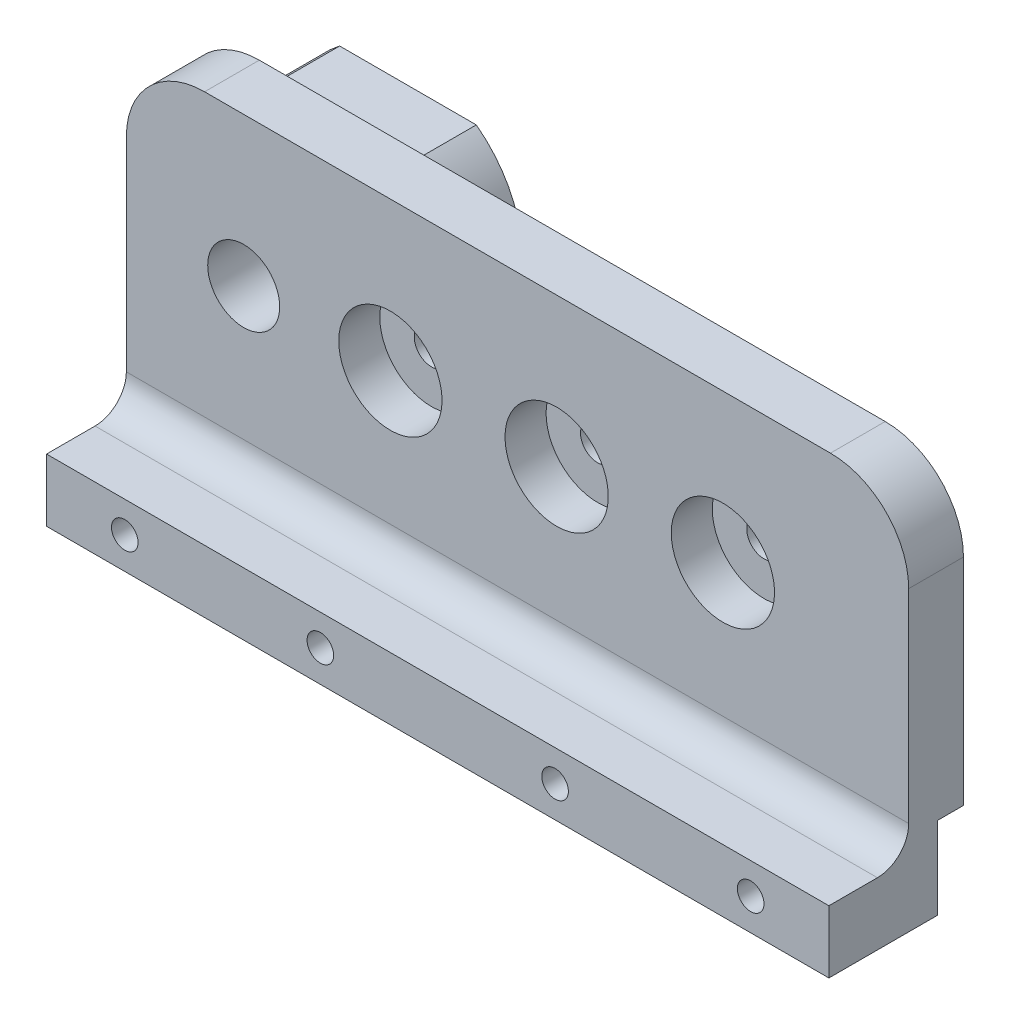
SolidWorks part; units mm, degrees
ref_plane "Front Plane" through (0, 0, 0) normal (0, 0, 1) x (1, 0, 0)
ref_plane "Top Plane" through (0, 0, 0) normal (0, 1, 0) x (1, 0, 0)
ref_plane "Right Plane" through (0, 0, 0) normal (1, 0, 0) x (0, 0, -1)
sketch "Sketch1" plane through (0, 0, 0) normal (0, 0, 1) x (1, 0, 0)
  line L1 (0, 0) -> (100, 0)
  line L2 (0, 0) -> (0, 48)
  line L3 (0, 48) -> (100, 48)
  line L4 (100, 0) -> (100, 48)
  dimension "D1" = 100
  dimension "D2" = 48
extrude "Boss-Extrude1" add sketch "Sketch1" along normal blind 7
sketch "Sketch2" plane through (0, 0, 7) normal (0, 0, 1) x (1, 0, 0)
  line L0 (0, 0) -> (100, 0) construction
  line L1 (0, 48) -> (0, 0) construction
  circle A0 centre (15, 29) radius 4.6
  circle A1 centre (33.75, 29) radius 2.2
  circle A2 centre (55, 29) radius 2.2
  circle A3 centre (76.25, 29) radius 2.2
  dimension "D1" = 4.4
  dimension "D2" = 18.75
  dimension "D3" = 21.25
  dimension "D4" = 21.25
  dimension "D5" = 29
  dimension "D6" = 15
  dimension "D7" = 9.2
extrude "Cut-Extrude1" cut sketch "Sketch2" against normal up to next
sketch "Sketch3" plane through (0, 0, 0) normal (0, 0, -1) x (-1, 0, 0)
  line L0 (0, 48) -> (0, 0) construction
  line L1 (-100, 0) -> (0, 0)
  line L2 (-100, 0) -> (-100, 8)
  line L3 (-100, 8) -> (0, 8)
  line L4 (0, 0) -> (0, 8)
  dimension "D1" = 8
extrude "Boss-Extrude2" add sketch "Sketch3" along normal blind 10.2
sketch "Sketch4" plane through (0, 0, 0) normal (0, 0, -1) x (-1, 0, 0)
  circle A0 centre (-76.25, 29) radius 6.6
  circle A1 centre (-55, 29) radius 6.6
  circle A2 centre (-33.75, 29) radius 6.6
  dimension "D1" = 13.2
extrude "Cut-Extrude2" cut sketch "Sketch4" against normal blind 5.25
sketch "Sketch5" plane through (0, 0, 7) normal (0, 0, 1) x (1, 0, 0)
  line L0 (35, 4.0521) -> (65, 4) construction
  line L1 (0, 0) -> (100, 0) construction
  circle A0 centre (35, 4.0521) radius 2.6
  circle A1 centre (65, 4) radius 2.6
  point P6 (50, 0)
  point P7 (50, 4.0261)
  dimension "D1" = 5.2
  dimension "D2" = 30
  dimension "D3" = 4
extrude "Cut-Extrude3" cut sketch "Sketch5" against normal blind 0.1
sketch "Sketch7" plane through (0, 0, 6.9) normal (0, 0, 1) x (1, 0, 0)
  circle A0 centre (35, 4.0521) radius 1.7
  circle A1 centre (65, 4) radius 1.7
  dimension "D1" = 3.4
extrude "Cut-Extrude4" cut sketch "Sketch7" against normal through all
sketch "Sketch8" plane through (0, 0, 7) normal (0, 0, 1) x (1, 0, 0)
  line L0 (10, 4.0521) -> (35, 4.0521) construction
  line L1 (0, 48) -> (0, 0) construction
  line L2 (100, 0) -> (100, 48) construction
  circle A0 centre (10, 4.0521) radius 1.7
  circle A1 centre (90, 4.0521) radius 1.7
  dimension "D1" = 3.4
  dimension "D2" = 10
  dimension "D3" = 10
extrude "Cut-Extrude5" cut sketch "Sketch8" against normal up to next
mirror "Mirror1" about plane through (0, 0, -10.2) normal (0, 0, 1) of bodies 110
delete or keep bodies "Body-Delete/Keep 1" type delete bodies bodies 110
sketch "Sketch9" plane through (100, 0, 0) normal (1, 0, 0) x (0, 0, -1)
  line L1 (27.4, 0) -> (24.1, 0)
  line L2 (27.4, 0) -> (27.4, 10.5)
  line L3 (27.4, 10.5) -> (24.1, 10.5)
  line L4 (24.1, 0) -> (24.1, 10.5)
  dimension "D1" = 10.5
  dimension "D2" = 3.3
extrude "Cut-Extrude6" cut sketch "Sketch9" against normal up to next
sketch "Sketch10" plane through (0, 0, -27.4) normal (0, 0, -1) x (-1, 0, 0)
  line L1 (-22.8594, 38.2) -> (-7.1406, 38.2)
  line L2 (-22.8594, 38.2) -> (-22.8594, 19.8) construction
  line L3 (-22.8594, 19.8) -> (-7.1406, 19.8)
  line L4 (-7.1406, 38.2) -> (-7.1406, 19.8) construction
  line L5 (-22.8594, 38.2) -> (-7.1406, 19.8) construction
  line L6 (-22.8594, 19.8) -> (-7.1406, 38.2) construction
  circle A0 centre (-15, 29) radius 12.1
  circle M6 centre (-15, 29) radius 4.6
  dimension "D2" = 24.2
  dimension "D1" = 18.4
extrude "Boss-Extrude3" add sketch "Sketch10" along normal blind 14 separate body contours L1 A0 L3 M6 | M6 region at (15, 37.896, -27.4) region at (15, 29, -27.4)
shell "Shell1" thickness 2.5 removed face at (15, 29, -27.4) removed face at (15, 29, -41.4) outward yes
combine bodies "Combine1" operation type add bodies to combine 115 116
fillet "Fillet3" radius 10 2 edges at (0, 48, -23.9) (100, 48, -23.9)
sketch "Sketch11" plane through (0, 0, -24.1) normal (0, 0, -1) x (-1, 0, 0)
  line L0 (-61.6513, 4) -> (-61.6513, 0)
  line L1 (-63.3257, 1.1) -> (-61.6513, 4) construction
  line L2 (-61.6513, 4) -> (-63.3257, 6.9)
  line L3 (-63.3257, 6.9) -> (-66.6743, 6.9)
  line L4 (-66.6743, 6.9) -> (-68.3486, 4)
  line L5 (-68.3486, 4) -> (-66.6743, 1.1) construction
  line L6 (-66.6743, 1.1) -> (-63.3257, 1.1) construction
  line L7 (0, 0) -> (-100, 0) construction
  line L8 (-68.3486, 4) -> (-68.3486, 0)
  line L9 (-61.6513, 0) -> (-68.3486, 0)
  line L10 (-38.2885, 4.0521) -> (-38.2885, 0)
  line L11 (-33.3558, 1.2043) -> (-31.7116, 4.0521) construction
  line L12 (-31.7116, 4.0521) -> (-33.3558, 6.9)
  line L13 (-33.3558, 6.9) -> (-36.6442, 6.9)
  line L14 (-36.6442, 6.9) -> (-38.2885, 4.0521)
  line L15 (-38.2885, 4.0521) -> (-36.6442, 1.2043) construction
  line L16 (-36.6442, 1.2043) -> (-33.3558, 1.2043) construction
  line L17 (-38.2885, 0) -> (-31.7116, 0)
  line L18 (-31.7116, 0) -> (-31.7116, 4.0521)
  circle A0 centre (-65, 4) radius 2.9 construction
  circle A1 centre (-35, 4.0521) radius 2.8479 construction
  dimension "D1" = 5.8
extrude "Cut-Extrude7" cut sketch "Sketch11" against normal blind 3.2 from offset 3 offset against normal yes
sketch "Sketch12" plane through (0, 0, -24.1) normal (0, 0, -1) x (-1, 0, 0)
  line L1 (-88.3257, 1.1521) -> (-86.6514, 4.0521)
  line L2 (-86.6514, 4.0521) -> (-88.3257, 6.9521)
  line L3 (-88.3257, 6.9521) -> (-91.6743, 6.9521)
  line L4 (-91.6743, 6.9521) -> (-93.3486, 4.0521)
  line L5 (-93.3486, 4.0521) -> (-91.6743, 1.1521)
  line L6 (-91.6743, 1.1521) -> (-88.3257, 1.1521)
  line L7 (-8.3257, 1.1521) -> (-6.6514, 4.0521)
  line L8 (-6.6514, 4.0521) -> (-8.3257, 6.9521)
  line L9 (-8.3257, 6.9521) -> (-11.6743, 6.9521)
  line L10 (-11.6743, 6.9521) -> (-13.3486, 4.0521)
  line L11 (-13.3486, 4.0521) -> (-11.6743, 1.1521)
  line L12 (-11.6743, 1.1521) -> (-8.3257, 1.1521)
  circle A0 centre (-90, 4.0521) radius 2.9 construction
  circle A1 centre (-10, 4.0521) radius 2.9 construction
  circle A2 centre (-10, 4.0521) radius 1.7 construction
  dimension "D1" = 5.8
extrude "Cut-Extrude8" cut sketch "Sketch12" against normal blind 5
fillet "Fillet4" radius 4 1 edges at (50, 8, -20.4)
